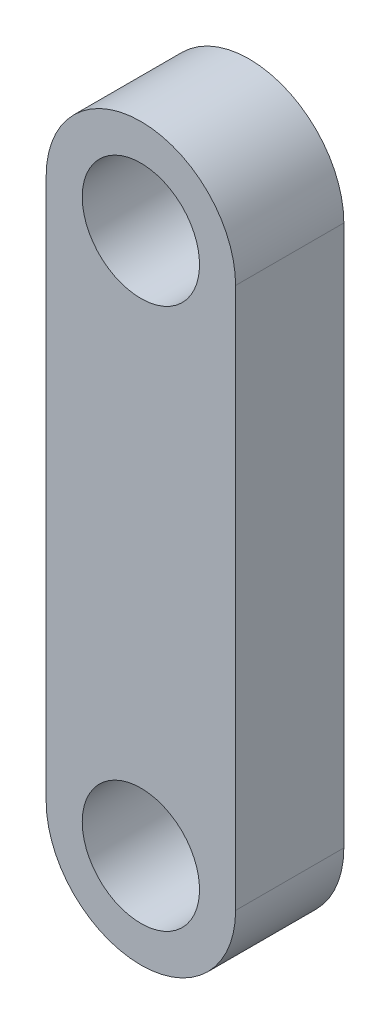
SolidWorks part; units mm, degrees
ref_plane "Front Plane" through (0, 0, 0) normal (0, 0, 1) x (1, 0, 0)
ref_plane "Top Plane" through (0, 0, 0) normal (0, 1, 0) x (1, 0, 0)
ref_plane "Right Plane" through (0, 0, 0) normal (1, 0, 0) x (0, 0, -1)
sketch "Sketch1" plane through (0, 0, 0) normal (0, 0, 1) x (1, 0, 0)
  line L1 (-5.25, 0) -> (-5.25, -30)
  line L2 (5.25, 0) -> (5.25, -30)
  circle A0 centre (0, 0) radius 3.25
  circle A1 centre (0, -30) radius 3.25
  arc A4 (-5.25, 0) -> (5.25, 0) centre (0, 0) cw
  arc A6 (-5.25, -30) -> (5.25, -30) centre (0, -30) ccw
extrude "Boss-Extrude1" add sketch "Sketch1" along normal blind 6 contours L1 A6 L2 A4
extrude "Cut-Extrude1" cut sketch "Sketch1<3>" along normal blind 16 contours A1 | A0 region at (0, -30, 0)
sketch "Sketch1<3>" plane through (0, 0, 0) normal (0, 0, 1) x (1, 0, 0) same geometry as "Sketch1"
